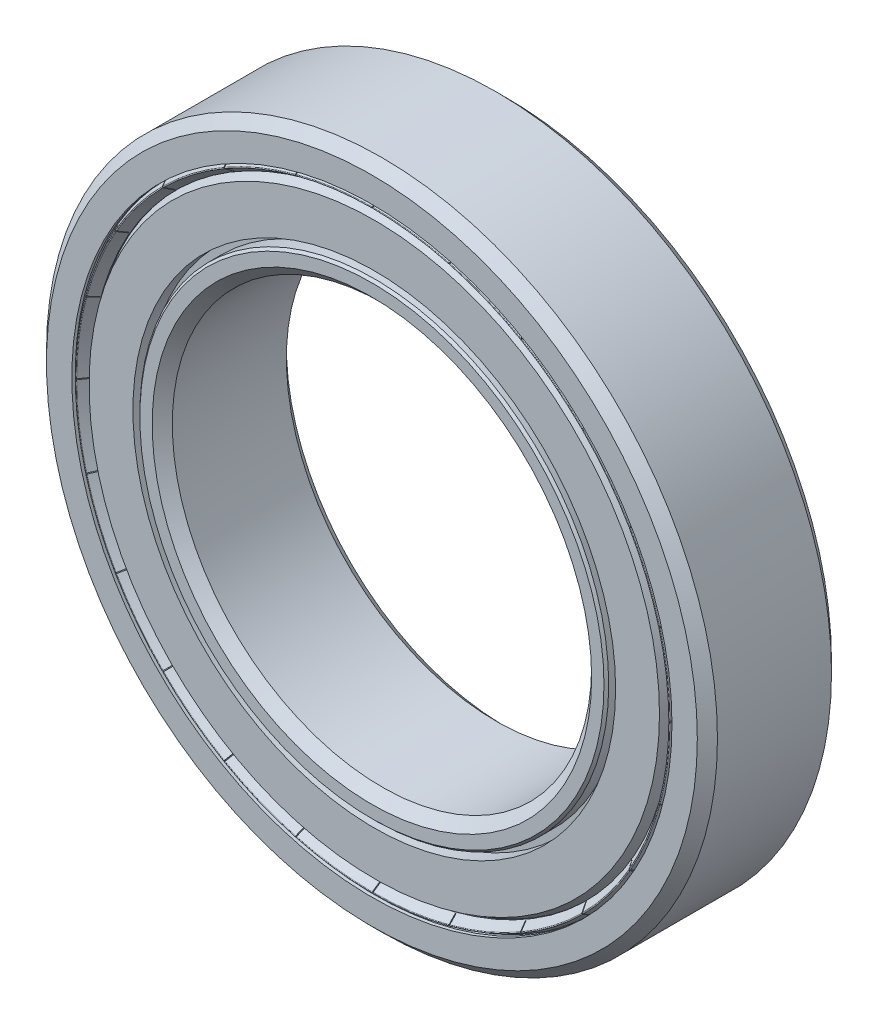
SolidWorks part; units mm, degrees
ref_plane "Front Plane" through (0, 0, 0) normal (0, 0, 1) x (1, 0, 0)
ref_plane "Top Plane" through (0, 0, 0) normal (0, 1, 0) x (1, 0, 0)
ref_plane "Right Plane" through (0, 0, 0) normal (1, 0, 0) x (0, 0, -1)
sketch "Sketch1" plane through (0, 0, 0) normal (0, 0, 1) x (1, 0, 0)
  circle A0 centre (0, 0) radius 25
  circle A1 centre (0, 0) radius 40
  dimension "OD" = 80
  dimension "ID" = 50
sketch "Sketch2" plane through (0, 0, 0) normal (1, 0, 0) x (0, 0, -1)
  line L0 (-8, 40) -> (8, 40)
  line L1 (-8, 25) -> (-8, -25) construction
  line L2 (8, 40) -> (8, -40) construction
  line L3 (-8, 0) -> (8, 0) construction
  line L6 (0, 40) -> (0, 25) construction
  circle A0 centre (0, 32.5) radius 5.25 construction
  point P8 (0, 40)
  dimension "Approx. Ball Dia." = 10.5
  dimension "Width" = 16
  dimension "For Shaft Diameter" = 50
  dimension "For Housing ID" = 80
sketch "Sketch3" plane through (0, 0, 0) normal (1, 0, 0) x (0, 0, -1)
  line L0 (0, 0) -> (0, 50) construction
  line L1 (-8, 25) -> (-8, -25) construction
  line L2 (6.8, 40) -> (-6.8, 40)
  line L3 (-6.8, 40) -> (-8, 38.8)
  line L4 (-8, 38.8) -> (-8, 35.7776)
  line L5 (-8, 35.7776) -> (-7.6, 35.7776)
  line L6 (-7.6, 35.7776) -> (-7.6, 36.7638)
  line L7 (-7.6, 36.7638) -> (-7.3172, 37.0466)
  line L8 (-7.3172, 37.0466) -> (-2.625, 37.0466)
  line L10 (-8, 40) -> (8, 40) construction
  line L12 (-7.6, 36.7638) -> (-7.6, 37.75) construction
  line L13 (7.3172, 37.0466) -> (2.625, 37.0466)
  line L14 (7.6, 36.7638) -> (7.3172, 37.0466)
  line L15 (7.6, 35.7776) -> (7.6, 36.7638)
  line L16 (8, 35.7776) -> (7.6, 35.7776)
  line L17 (8, 38.8) -> (8, 35.7776)
  line L18 (6.8, 40) -> (8, 38.8)
  line L19 (6.8, 25) -> (-6.8, 25)
  line L20 (-6.8, 25) -> (-8, 26.2)
  line L21 (-8, 26.2) -> (-8, 27.6705)
  line L22 (-8, 27.6705) -> (-7.7172, 27.9534)
  line L23 (-7.7172, 27.9534) -> (-2.625, 27.9534)
  line L25 (7.7172, 27.9534) -> (2.625, 27.9534)
  line L26 (8, 27.6705) -> (7.7172, 27.9534)
  line L27 (8, 26.2) -> (8, 27.6705)
  line L28 (6.8, 25) -> (8, 26.2)
  circle A2 centre (0, 32.5) radius 5.25 construction
  arc A3 (-2.625, 37.0466) -> (2.625, 37.0466) centre (0, 32.5) cw
  arc A4 (-2.625, 27.9534) -> (2.625, 27.9534) centre (0, 32.5) ccw
  point P5 (0, 37.75)
  point P31 (0, 40)
  point P37 (0, 25)
  dimension "D1" = 45
  dimension "D2" = 0.4
  dimension "D3" = 5.25
  dimension "D4" = 1.2
revolve "Revolve1" add sketch "Sketch3" angle 360 about L3
sketch "Sketch4" plane through (0, 0, 0) normal (1, 0, 0) x (0, 0, -1)
  line L0 (0, 37.75) -> (0, 27.25)
  line L1 (0, 40) -> (0, 25) construction
  circle A0 centre (0, 32.5) radius 5.25 construction
  arc A1 (0, 27.25) -> (0, 37.75) centre (0, 32.5) cw
revolve "Revolve2" add sketch "Sketch4" angle 360 about L6
pattern_circular "CirPattern1" count 12 over 360 about axis through (0, 0, 8) along (0, 0, -1) of bodies 106
sketch "Sketch5" plane through (0, 0, 0) normal (1, 0, 0) x (0, 0, -1)
  line L0 (-5.25, 32.5) -> (-5.25, 27.9534) construction
  line L1 (-7.7172, 27.9534) -> (-2.625, 27.9534) construction
  line L3 (-5.25, 27.9534) -> (-6.0724, 27.9534)
  line L4 (-6.0724, 27.9534) -> (-6.0724, 28.7758)
  line L5 (-6.0724, 28.7758) -> (-7.7172, 28.7758)
  line L6 (-7.7172, 28.7758) -> (-7.7172, 34.0056)
  line L7 (-7.7172, 34.0056) -> (-6.0724, 34.9552)
  line L8 (-6.0724, 34.9552) -> (-5.25, 34.9552)
  line L9 (-5.25, 34.9552) -> (-5.25, 27.9534)
  line L10 (0, 32.5) -> (0, 40) construction
  line L11 (6.0724, 34.9552) -> (5.25, 34.9552)
  line L12 (7.7172, 34.0056) -> (6.0724, 34.9552)
  line L13 (7.7172, 28.7758) -> (7.7172, 34.0056)
  line L14 (6.0724, 28.7758) -> (7.7172, 28.7758)
  line L15 (6.0724, 27.9534) -> (6.0724, 28.7758)
  line L16 (5.25, 27.9534) -> (6.0724, 27.9534)
  line L17 (5.25, 34.9552) -> (5.25, 27.9534)
  line L18 (-7.7172, 34.0056) -> (-6.8948, 34.0056) construction
  line L19 (-6.8948, 34.0056) -> (-6.0724, 34.0056) construction
  line L20 (-6.0724, 34.0056) -> (-5.25, 34.0056) construction
  line L21 (-6.0724, 34.9552) -> (-6.0724, 35.7776) construction
  circle A0 centre (0, 32.5) radius 5.25 construction
  dimension "D1" = 30
revolve "Revolve3" add sketch "Sketch5" angle 360 about L3
sketch "Sketch6" plane through (0, 0, 0) normal (1, 0, 0) x (0, 0, -1)
  line L0 (-6.6479, 35.7776) -> (-7.3, 35.7776)
  line L1 (-7.3, 35.7776) -> (-8, 35.3734)
  line L2 (-8, 35.3734) -> (-6.8879, 34.5947)
  line L4 (-7.7172, 34.0056) -> (-6.0724, 34.9552) construction
  line L5 (-6.6479, 34.6229) -> (-6.6479, 35.7776)
  line L6 (-8, 35.7776) -> (-7.6, 35.7776) construction
  line L7 (-6.8879, 34.5947) -> (-6.8079, 34.5947)
  line L8 (-6.8079, 34.5947) -> (-6.6479, 34.6229)
  line L9 (-8, 38.8) -> (-8, -38.8) construction
  line L11 (-6.8079, 34.5947) -> (-6.7279, 34.5947) construction
  line L12 (-6.7279, 34.5947) -> (-6.6479, 34.5947) construction
  point P27 (-6.9739, 35.7776)
  dimension "D1" = 30
  dimension "D3" = 10
  dimension "D2" = 35
  dimension "D4" = 0.08
  dimension "D5" = 0.7
revolve "Revolve4" add sketch "Sketch6" angle 360 about L3
fillet "Fillet1" radius 0.08 1 edges at (35.3734, 0, 8)
sketch "Sketch7" plane through (0, 0, 0) normal (0, 0, 1) x (1, 0, 0)
  line L0 (-0.05, 35.7776) -> (-0.05, 35.8776)
  line L1 (-0.05, 35.7776) -> (0.05, 35.7776) construction
  line L2 (-0.05, 35.7776) -> (-0.05, 34.5947)
  line L3 (-0.05, 34.5947) -> (0.05, 34.5947) construction
  line L4 (0.05, 35.7776) -> (0.05, 34.5947)
  line L5 (-0.05, 35.8776) -> (0.05, 35.8776)
  line L6 (0.05, 35.8776) -> (0.05, 35.7776)
  line L7 (-0.05, 34.5947) -> (-0.05, 34.4947)
  line L8 (-0.05, 34.4947) -> (0.05, 34.4947)
  line L9 (0.05, 34.4947) -> (0.05, 34.5947)
  dimension "D1" = 0.1
extrude "Cut-Extrude1" cut sketch "Sketch7" along normal through all from vertex starting at point (0, 35.7776, 6.9739)
pattern_circular "CirPattern2" count 24 over 360 about axis through (0, 0, 8) along (0, 0, -1) of "Cut-Extrude1"
mirror "Mirror1" about plane through (0, 0, 0) normal (0, 0, 1) of bodies 120
equation "\"Approx. Ball Dia.@Sketch2\"=( \"OD@Sketch1\" - \"ID@Sketch1\" )  * .5 * .7"
equation "\"D2@Sketch3\"=\"Width@Sketch2\"*.025"
equation "\"D3@Sketch3\"=\"Approx. Ball Dia.@Sketch2\"*.5"
equation "\"D4@Sketch3\"=\"Width@Sketch2\"*.075"
equation "\"Approx No of Balls\"= ( pi * \"OD@Sketch1\" ) * .5 / \"Approx. Ball Dia.@Sketch2\""
equation "\"D1@CirPattern1\"=\"Approx No of Balls\""
equation "\"D4@Sketch6\"=\"D2@Sketch3\"*.2"
equation "\"D1@CirPattern2\"=\"Approx No of Balls\"*2"
equation "\"D5@Sketch6\"=\"D2@Sketch3\"*1.75"
equation "\"D1@Fillet1\"=\"d4@sketch6\""
